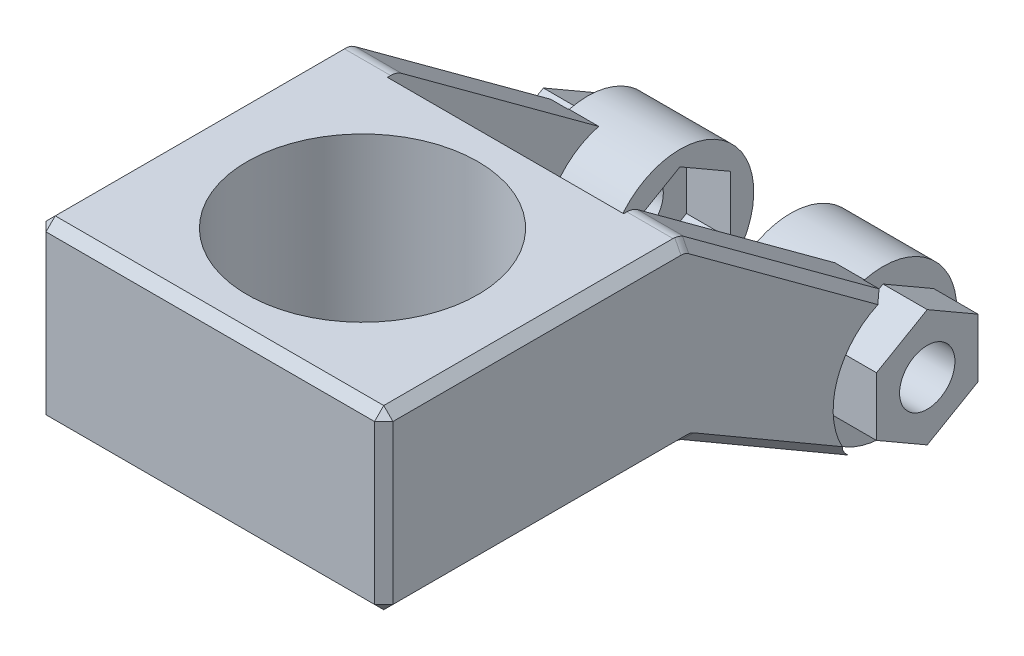
SolidWorks part; units mm, degrees
ref_plane "Front Plane" through (0, 0, 0) normal (0, 0, 1) x (1, 0, 0)
ref_plane "Top Plane" through (0, 0, 0) normal (0, 1, 0) x (1, 0, 0)
ref_plane "Right Plane" through (0, 0, 0) normal (1, 0, 0) x (0, 0, -1)
sketch "Sketch1" plane through (0, 0, 0) normal (0, 1, 0) x (1, 0, 0)
  line L0 (-9.4, 13.1461) -> (-9.4, -15.9532) construction
  line L1 (-19.9267, 0) -> (20.4407, 0) construction
  line L2 (-8.1549, 15.4287) -> (-8.1549, -9.8751) construction
  line L3 (0, -6.25) -> (-8.1549, -6.25) construction
  line L4 (-8.1549, -6.25) -> (-10.7947, -0.8827) construction
  line L5 (0, 6.25) -> (-8.1549, 6.25) construction
  line L6 (-8.1549, 6.25) -> (-10.7947, 0.8827) construction
  line L7 (0, 8.25) -> (-9.4, 8.25)
  line L9 (0, -8.25) -> (-9.4, -8.25)
  line L11 (0, 8.25) -> (0, 6.25)
  line L12 (0, -8.25) -> (0, -6.25)
  line L13 (-9.4, -8.25) -> (-12.5894, -1.7654) construction
  line L14 (-9.4, 8.25) -> (-12.5894, 1.7654) construction
  line L15 (-9.4, -8.25) -> (-9.4, 8.25)
  circle A0 centre (0, 0) radius 6.25 construction
  circle A2 centre (-9, 0) radius 2 construction
  circle A3 centre (-9, 0) radius 4 construction
  arc A5 (0, 6.25) -> (0, -6.25) centre (0, 0) ccw
  dimension "D1" = 12.5
  dimension "D5" = 4
  dimension "D2" = 9.4
  dimension "D3" = 9
  dimension "D7" = 2
  dimension "D8" = 2
  dimension "D9" = 2
extrude "Bracket" add sketch "Sketch1" along normal blind 0.1
ref_plane "Arm Plane" through (-6.4, 0, 0) normal (1, 0, 0) x (0, 0, -1)
sketch "Sketch2" plane through (-6.4, 0, 0) normal (1, 0, 0) x (0, 0, -1)
  line L1 (-8.25, 0) -> (18.1909, -15.3588)
  line L2 (8.25, 0) -> (19.2, -8.027)
  line L5 (-8.25, 0) -> (8.25, 0)
  circle A0 centre (20.2, -11.9) radius 4 construction
  arc A1 (18.1909, -15.3588) -> (19.2, -8.027) centre (20.2, -11.9) ccw
  circle A2 centre (20.2, -11.9) radius 1.5
  dimension "D1" = 8
  dimension "D4" = 3
  dimension "D2" = 20.2
  dimension "D3" = 11.9
  dimension "D5" = 1
extrude "Arm" add sketch "Sketch2" against normal blind 1.6
sketch "Sketch4" plane through (-8, 0, 0) normal (-1, 0, 0) x (0, 0, 1)
  circle A0 centre (-20.2, -11.9) radius 4
  circle A1 centre (-20.2, -11.9) radius 1.5
  circle A2 centre (-20.2, -11.9) radius 1.5 construction
  arc A3 (-19.2, -8.027) -> (-18.1909, -15.3588) centre (-20.2, -11.9) ccw construction
extrude "Effector Mount" add sketch "Sketch4" against normal blind 5
sketch "Sketch5" plane through (-3, 0, 0) normal (1, 0, 0) x (0, 0, -1)
  line L1 (20.2, -8.7246) -> (17.45, -10.3123)
  line L2 (17.45, -10.3123) -> (17.45, -13.4877)
  line L3 (17.45, -13.4877) -> (20.2, -15.0754)
  line L4 (20.2, -15.0754) -> (22.95, -13.4877)
  line L5 (22.95, -13.4877) -> (22.95, -10.3123)
  line L6 (22.95, -10.3123) -> (20.2, -8.7246)
  circle A0 centre (20.2, -11.9) radius 2.75 construction
  dimension "D1" = 5.5
extrude "Mount Trap" cut sketch "Sketch5" against normal blind 2.4
sketch "Sketch6" plane through (-8, 0, 0) normal (-1, 0, 0) x (0, 0, 1)
  line L1 (-17.45, -10.3123) -> (-20.2, -8.7246)
  line L2 (-20.2, -8.7246) -> (-22.95, -10.3123)
  line L3 (-22.95, -10.3123) -> (-22.95, -13.4877)
  line L4 (-22.95, -13.4877) -> (-20.2, -15.0754)
  line L5 (-20.2, -15.0754) -> (-17.45, -13.4877)
  line L6 (-17.45, -13.4877) -> (-17.45, -10.3123)
  circle A0 centre (-20.2, -11.9) radius 2.75 construction
  circle A1 centre (-20.2, -11.9) radius 1.5
  circle A2 centre (-20.2, -11.9) radius 1.5 construction
  dimension "D1" = 5.5
extrude "Mount Adaptor" add sketch "Sketch6" along normal blind 2.4
sketch "Sketch7" plane through (-8, 0, 0) normal (-1, 0, 0) x (0, 0, 1)
  line L0 (-8.25, 0) -> (-19.0966, -7.9513)
  line L1 (-19.2, -8.027) -> (-8.25, 0) construction
  line L2 (8.25, 0) -> (-17.4126, -14.9068)
  line L3 (8.25, 0) -> (-18.1909, -15.3588) construction
  line L4 (-8.25, 0) -> (8.25, 0)
  line L5 (8.25, 0.1) -> (8.25, 0) construction
  circle A0 centre (-20.2, -11.9) radius 4.1 construction
  arc A1 (-19.0966, -7.9513) -> (-17.4126, -14.9068) centre (-20.2, -11.9) cw
  dimension "D1" = 8.2
extrude "Arm Support" add sketch "Sketch7" along normal blind 1.4
sketch "Sketch9" plane through (0, 0, 0) normal (0, -1, 0) x (1, 0, 0)
  line L5 (-6.4, 8.25) -> (-9.4, 8.25)
  line L6 (-9.4, 8.25) -> (-9.4, -8.25)
  line L7 (-9.4, -17.4126) -> (-9.4, 8.25) construction
  line L8 (-6.4, -8.25) -> (-9.4, -8.25)
  line L10 (-6.4, 8.25) -> (-6.4, -8.25)
  line L11 (-6.4, -8.25) -> (0, -8.25)
  line L12 (0, -8.25) -> (0, -6.25)
  line L13 (0, 6.25) -> (0, 8.25)
  line L14 (0, 8.25) -> (-6.4, 8.25)
  line L16 (-6.4, -8.25) -> (0, -8.25)
  line L17 (0, -8.25) -> (0, -6.25)
  line L18 (0, 6.25) -> (0, 8.25)
  line L19 (0, 8.25) -> (-6.4, 8.25)
  arc A2 (0, 6.25) -> (0, -6.25) centre (0, 0) ccw
  arc A3 (0, 6.25) -> (0, -6.25) centre (0, 0) ccw
  point P2 (0, 0)
  dimension "D1" = 0
extrude "Boss-Extrude1" add sketch "Sketch9" along normal blind 9.5844
mirror "Mirror8" about plane through (0, 0, 0) normal (1, 0, 0) of "Boss-Extrude1", "Arm Support", "Mount Adaptor", "Mount Trap", "Effector Mount", "Arm", "Bracket"
sketch "Sketch13" plane through (9.4, 0, 0) normal (1, 0, 0) x (0, 0, -1)
  line L1 (-8.25, 0.1) -> (8.25, 0.1)
  line L2 (-8.25, 0.1) -> (-8.25, 0)
  line L3 (-8.25, 0) -> (8.25, 0)
  line L4 (8.25, 0.1) -> (8.25, 0)
extrude "Cut-Extrude2" cut sketch "Sketch13" against normal through all
chamfer "Chamfer8" distance 0.5 angle 45 13 edges at (-9.4, -12.2456, -12.8313) (-9.4, -9.5844, 0) (-9.4, -4.7922, 8.25) (0, -9.5844, 8.25) (-9.4, -3.9756, -13.6733) (-9.4, 0, 0) (0, 0, 8.25) (9.4, -12.2456, -12.8313) (9.4, -9.5844, 0) (9.4, -4.7922, 8.25) (9.4, -3.9756, -13.6733) (9.4, 0, 0) (0, 0, -8.25)
chamfer "Chamfer9" distance 0.5 angle 45 1 edges at (0, -9.5844, -8.25)
sketch "Sketch14" plane through (6.4, 0, 0) normal (-1, 0, 0) x (0, 0, 1)
  line L0 (-7.75, -9.5844) -> (-8.25, -9.5844)
  line L1 (-8.25, -9.5844) -> (-17.4126, -14.9068) construction
  line L2 (-8.25, -9.5844) -> (-7.9337, -9.4007)
  line L3 (-7.9337, -9.4007) -> (-7.75, -9.5844)
extrude "Boss-Extrude3" add sketch "Sketch14" against normal up to surface (15.4837 mm away) up to face at (9.0973, -9.3871, -2.8031)
sketch "Sketch15" plane through (-6.4, 0, 0) normal (1, 0, 0) x (0, 0, -1)
  line L0 (8.25, -9.5844) -> (7.75, -9.5844)
  line L1 (7.9337, -9.4007) -> (18.1909, -15.3588) construction
  line L2 (7.75, -9.5844) -> (7.9337, -9.4007)
  line L3 (7.9337, -9.4007) -> (8.25, -9.5844)
  line L4 (8.25, -9.5844) -> (-7.75, -9.5844) construction
  point P4 (0, 0)
  point P9 (0, 0)
extrude "Boss-Extrude4" add sketch "Sketch15" against normal up to surface (2.6837 mm away) up to face at (-9.0973, -9.3871, -2.8031)
fillet "Fillet2" radius 1 8 edges at (9.15, -0.25, -8.1682) (-9.15, -0.25, -8.1682) (-7.65, 0, -8.25) (7.65, 0, -8.25) (7.65, -9.5844, -8.25) (9.15, -9.3344, -8.3173) (-9.15, -9.3344, -8.3173) (-7.65, -9.5844, -8.25)
